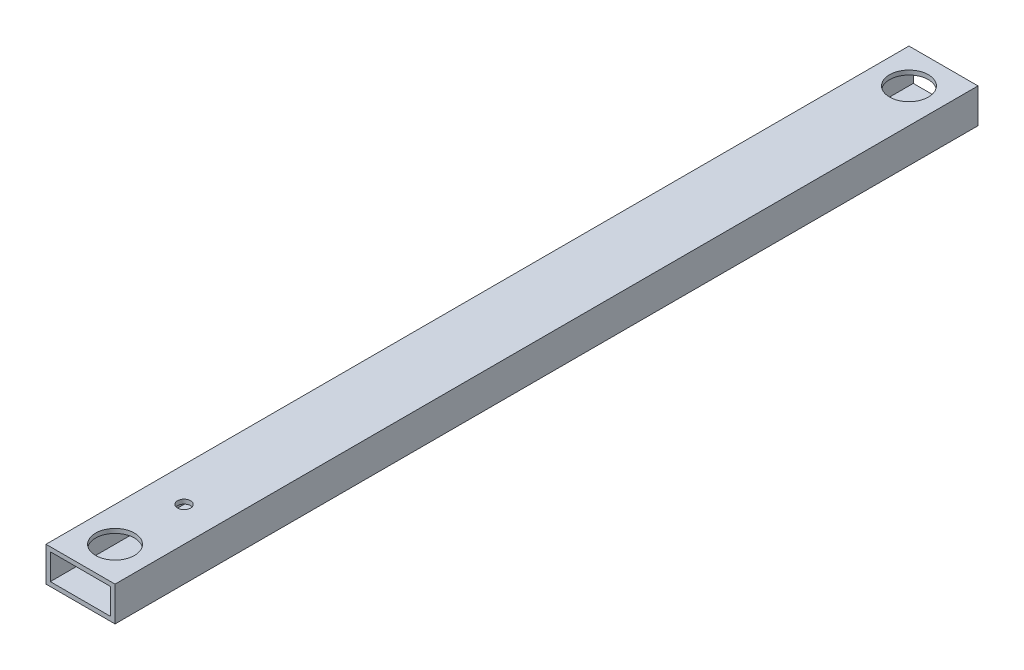
SolidWorks part; units mm, degrees
ref_plane "Front Plane" through (0, 0, 0) normal (0, 0, 1) x (1, 0, 0)
ref_plane "Top Plane" through (0, 0, 0) normal (0, 1, 0) x (1, 0, 0)
ref_plane "Right Plane" through (0, 0, 0) normal (1, 0, 0) x (0, 0, -1)
sketch "Sketch1" plane through (0, 0, 0) normal (0, 0, 1) x (1, 0, 0)
  line L1 (0, 0) -> (50.8, 0)
  line L2 (0, 0) -> (0, 25.4)
  line L3 (0, 25.4) -> (50.8, 25.4)
  line L4 (50.8, 0) -> (50.8, 25.4)
extrude "Boss-Extrude1" add sketch "Sketch1" along normal blind 635
sketch "Sketch2" plane through (0, 0, 0) normal (0, 0, -1) x (-1, 0, 0)
  line L1 (-3.175, 3.175) -> (-47.625, 3.175)
  line L2 (-3.175, 3.175) -> (-3.175, 22.225)
  line L3 (-3.175, 22.225) -> (-47.625, 22.225)
  line L4 (-47.625, 3.175) -> (-47.625, 22.225)
extrude "Cut-Extrude1" cut sketch "Sketch2" against normal blind 635
sketch "Sketch6" plane through (0, 25.4, 0) normal (0, 1, 0) x (1, 0, 0)
  line L0 (25.4, 0) -> (25.4, -25.4) construction
  line L1 (50.8, 0) -> (0, 0) construction
  circle A0 centre (25.4, -25.4) radius 14.2875
extrude "Cut-Extrude5" cut sketch "Sketch6" against normal blind 3.175
sketch "Sketch7" plane through (0, 25.4, 0) normal (0, 1, 0) x (1, 0, 0)
  line L0 (25.4, -635) -> (25.4, -609.6) construction
  line L1 (50.8, -635) -> (0, -635) construction
  circle A0 centre (25.4, -609.6) radius 14.2875
extrude "Cut-Extrude6" cut sketch "Sketch7" against normal blind 3.175
sketch "Sketch8" plane through (0, 0, 0) normal (0, -1, 0) x (-1, 0, 0)
  line L0 (-25.4, -635) -> (-25.4, -558.8) construction
  line L1 (0, -635) -> (-50.8, -635) construction
  circle A0 centre (-25.4, -558.8) radius 4.7625
extrude "Cut-Extrude7" cut sketch "Sketch8" against normal blind 25.4
